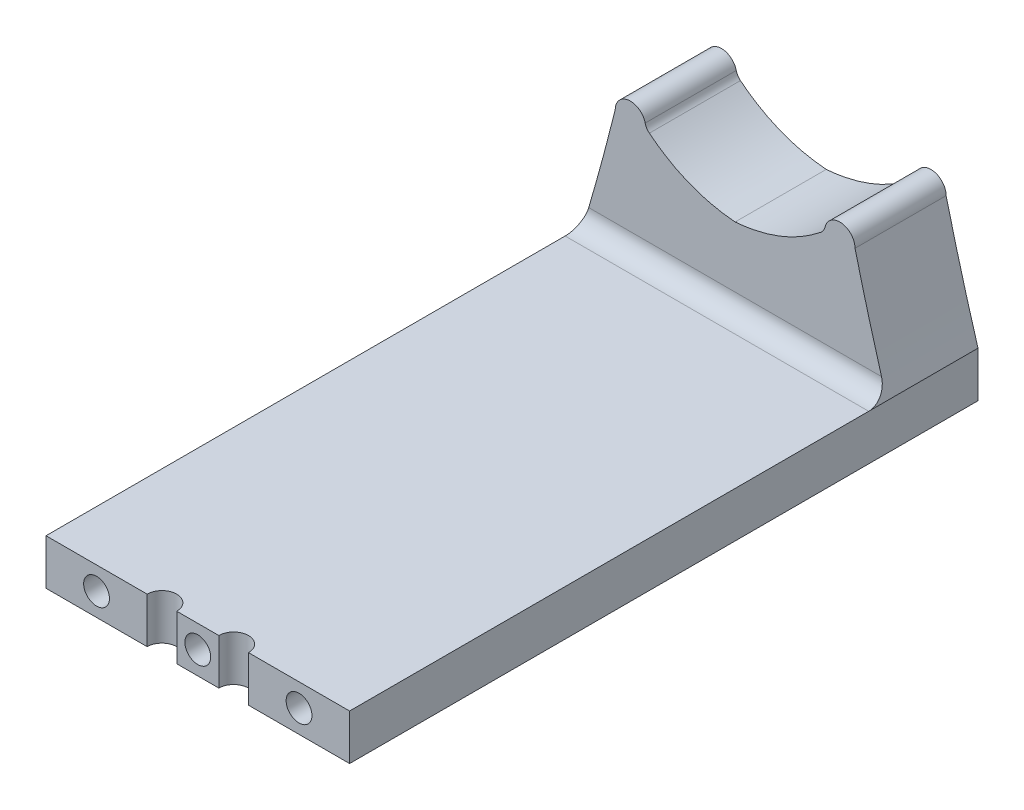
SolidWorks part; units mm, degrees
ref_plane "Front Plane" through (0, 0, 0) normal (0, 0, 1) x (1, 0, 0)
ref_plane "Top Plane" through (0, 0, 0) normal (0, 1, 0) x (1, 0, 0)
ref_plane "Right Plane" through (0, 0, 0) normal (1, 0, 0) x (0, 0, -1)
sketch "Sketch1" plane through (0, 0, 0) normal (0, 0, 1) x (1, 0, 0)
  line L0 (-996.8903, -40.64) -> (49003.1097, -40.64) construction
  line L1 (0, -1000) -> (0, 49000) construction
  line L2 (0, 0) -> (-23.4635, -40.64) construction
  line L3 (0, 0) -> (-40.64, -40.64) construction
  line L4 (-31.75, -62.23) -> (-31.75, -71.755)
  line L5 (-31.75, -71.755) -> (31.75, -71.755)
  line L6 (31.75, -62.23) -> (31.75, -71.755)
  line L7 (-957.5735, -46.99) -> (49042.4265, -46.99) construction
  circle A0 centre (0, 0) radius 40.64 construction
  arc A1 (-18.7325, -37.9449) -> (-25.0825, -37.9449) centre (-21.9075, -37.9449) ccw
  arc A2 (18.7325, -37.9449) -> (25.0825, -37.9449) centre (21.9075, -37.9449) cw
  spline S0 degree 2 poles (-18.7325, -37.9449) (-10.6333, -44.8669) (0, -45.72) knots 0 0 0 1 1 1
  spline S1 degree 2 poles (-25.0825, -37.9449) (-28.1202, -50.167) (-31.75, -62.23) knots 0 0 0 1 1 1
  spline S2 degree 2 poles (25.0825, -37.9449) (28.1202, -50.167) (31.75, -62.23) knots 0 0 0 1 1 1
  spline S3 degree 2 poles (18.7325, -37.9449) (10.6333, -44.8669) (0, -45.72) knots 0 0 0 1 1 1
  point P13 (0, -71.755)
  dimension "D1" = 81.28
  dimension "D3" = 6.35
  dimension "D5" = 5.08
  dimension "D2" = 30
  dimension "D4" = 45
  dimension "D6" = 31.75
  dimension "D7" = 9.525
  dimension "D8" = 21.59
  dimension "D9" = 6.35
extrude "Boss-Extrude1" add sketch "Sketch1" along normal mid plane 19.05
sketch "Sketch2" plane through (0, 0, 0) normal (0, 0, 1) x (1, 0, 0)
  line L1 (-31.75, -62.23) -> (31.75, -62.23)
  line L2 (-31.75, -62.23) -> (-31.75, -71.755)
  line L3 (-31.75, -71.755) -> (31.75, -71.755)
  line L4 (31.75, -62.23) -> (31.75, -71.755)
extrude "Boss-Extrude2" add sketch "Sketch2" along normal blind 121.92
fillet "Fillet2" radius 2.54 2 edges at (18.7325, -37.9449, 0) (-18.7325, -37.9449, 0)
sketch "Sketch3" plane through (0, -62.23, 0) normal (0, 1, 0) x (1, 0, 0)
  line L0 (31.75, -121.92) -> (-31.75, -121.92) construction
  line L1 (0, -9.525) -> (0, 9.525) construction
  circle A0 centre (7.5, -121.92) radius 3.1
  circle A1 centre (-7.5, -121.92) radius 3.1
  dimension "D1" = 6.2
  dimension "D2" = 7.5
extrude "Cut-Extrude1" cut sketch "Sketch3" against normal through all
ref_plane "wheel_tangent_plane" through (0, -40.64, 0) normal (0, 1, 0) x (1, 0, 0)
ref_plane "offset_0.1in_aka_poly_top" through (0, -43.18, 0) normal (0, 1, 0) x (1, 0, 0)
sketch "Sketch4" plane through (0, 0, 121.92) normal (0, 0, 1) x (1, 0, 0)
  circle A0 centre (-21.175, -66.9925) radius 2.7
  circle A1 centre (0, -66.9925) radius 2.7
  circle A2 centre (21.175, -66.9925) radius 2.7
  dimension "D1" = 5.4
  dimension "D2" = 5.4
  dimension "D3" = 5.4
extrude "Cut-Extrude2" cut sketch "Sketch4" against normal blind 9.525
fillet "Fillet3" radius 3.81 1 edges at (0, -62.23, 9.525) type face fillet first side face at (2.7343, -43.5854, 9.525) second side face at (0, -62.23, 93.0463)
